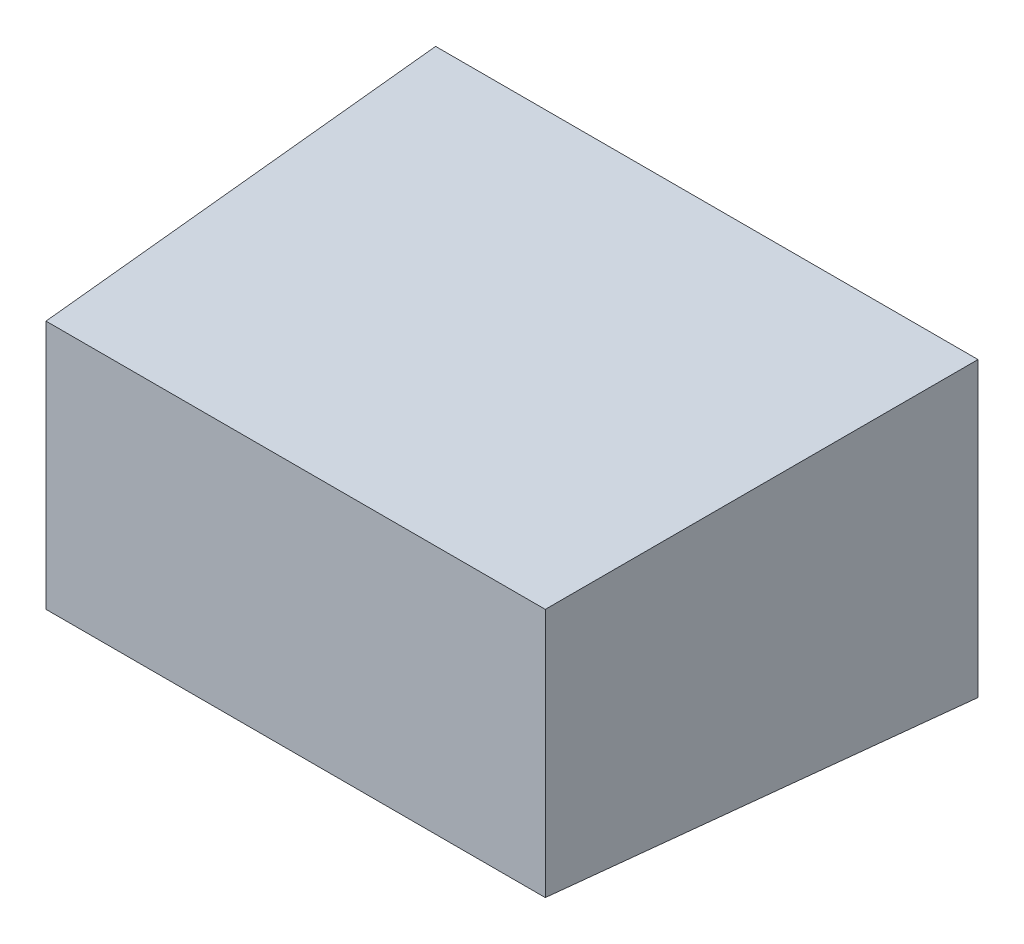
SolidWorks part; units mm, degrees
material "ABS PC"
ref_plane "Front Plane" through (0, 0, 0) normal (0, 0, 1) x (1, 0, 0)
ref_plane "Top Plane" through (0, 0, 0) normal (0, 1, 0) x (1, 0, 0)
ref_plane "Right Plane" through (0, 0, 0) normal (1, 0, 0) x (0, 0, -1)
sketch "Sketch1" plane through (0, 0, 0) normal (0, 0, 1) x (1, 0, 0)
  line L1 (-110.3399, 56.695) -> (79.6601, 56.695)
  line L2 (-110.3399, 56.695) -> (-110.3399, -48.305)
  line L3 (-110.3399, -48.305) -> (79.6601, -48.305)
  line L4 (79.6601, 56.695) -> (79.6601, -48.305)
  dimension "D1" = 190
  dimension "D2" = 105
extrude "Boss-Extrude1" add sketch "Sketch1" along normal blind 140
chamfer "Chamfer1" distance 10 angle 87 4 edges at (-15.3399, 56.695, 140) (79.6601, 4.195, 140) (-15.3399, -48.305, 140) (-110.3399, 4.195, 140) first distance on face at (-15.3399, 4.195, 140)
shell "Shell1" thickness 3 removed face at (-15.3399, 4.195, 0)
